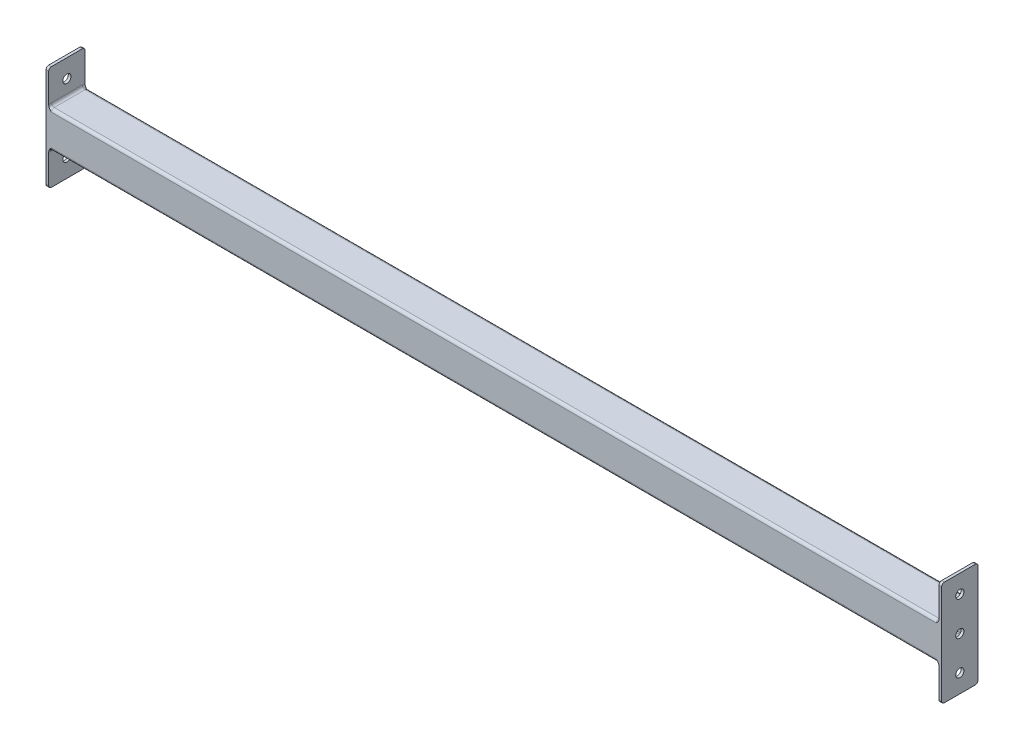
SolidWorks part; units mm, degrees
ref_plane "Front Plane" through (0, 0, 0) normal (0, 0, 1) x (1, 0, 0)
ref_plane "Top Plane" through (0, 0, 0) normal (0, 1, 0) x (1, 0, 0)
ref_plane "Right Plane" through (0, 0, 0) normal (1, 0, 0) x (0, 0, -1)
sketch "Sketch1" plane through (0, 0, 0) normal (1, 0, 0) x (0, 0, -1)
  line L1 (-20, -20) -> (20, -20)
  line L2 (-20, -20) -> (-20, 20)
  line L3 (-20, 20) -> (20, 20)
  line L4 (20, -20) -> (20, 20)
  line L5 (-20, -20) -> (20, 20) construction
  line L6 (-20, 20) -> (20, -20) construction
  line L7 (-17, -17) -> (17, -17)
  line L8 (-17, -17) -> (-17, 17)
  line L9 (-17, 17) -> (17, 17)
  line L10 (17, -17) -> (17, 17)
  line L11 (-17, -17) -> (17, 17) construction
  line L12 (-17, 17) -> (17, -17) construction
  point P0 (0, 0)
  point P6 (0, 0)
  dimension "D1" = 40
  dimension "D2" = 3
extrude "Boss-Extrude1" add sketch "Sketch1" along normal blind 489.5
fillet "Fillet1" radius 1 4 edges at (244.75, -17, -17) (244.75, 17, -17) (244.75, 17, 17) (244.75, -17, 17)
fillet "Fillet2" radius 3 4 edges at (244.75, -20, 20) (244.75, -20, -20) (244.75, 20, -20) (244.75, 20, 20)
sketch "Sketch2" plane through (489.5, 0, 0) normal (1, 0, 0) x (0, 0, -1)
  line L0 (0, -37.5) -> (0, 37.5) construction
  line L1 (-20, -57.5) -> (20, -57.5)
  line L2 (-20, -57.5) -> (-20, 57.5)
  line L3 (-20, 57.5) -> (20, 57.5)
  line L4 (20, -57.5) -> (20, 57.5)
  line L5 (-20, -57.5) -> (20, 57.5) construction
  line L6 (-20, 57.5) -> (20, -57.5) construction
  line L7 (-20, 57.5) -> (0, 37.5) construction
  line L8 (0, 37.5) -> (20, 57.5) construction
  circle A0 centre (0, 0) radius 4.5
  circle A1 centre (0, -37.5) radius 4.5
  circle A2 centre (0, 37.5) radius 4.5
  point P0 (0, 0)
  point P13 (0, 0)
  dimension "D3" = 9
  dimension "D1" = 40
  dimension "D2" = 75
extrude "Boss-Extrude2" add sketch "Sketch2" along normal blind 3
fillet "Fillet3" radius 3 6 edges at (489.5, -19.1213, 19.1213) (489.5, -20, 0) (489.5, 19.1213, -19.1213) (489.5, 19.1213, 19.1213) (489.5, -19.1213, -19.1213) (489.5, 20, 0)
fillet "Fillet4" radius 3 4 edges at (491, -57.5, -20) (491, -57.5, 20) (491, 57.5, 20) (491, 57.5, -20)
mirror "Mirror1" about plane through (0, 0, 0) normal (1, 0, 0) of bodies 102
